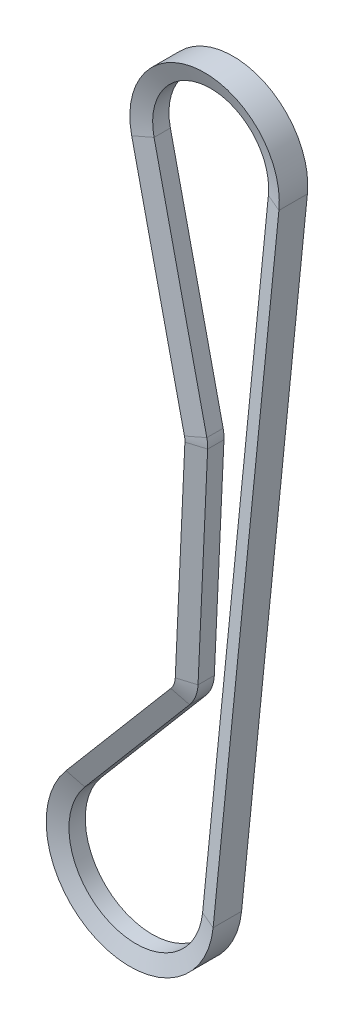
SolidWorks part; units mm, degrees
ref_plane "Front Plane" through (0, 0, 0) normal (0, 0, 1) x (1, 0, 0)
ref_plane "Top Plane" through (0, 0, 0) normal (0, 1, 0) x (1, 0, 0)
ref_plane "Right Plane" through (0, 0, 0) normal (1, 0, 0) x (0, 0, -1)
sketch "Sketch2" plane through (0, 0, 0) normal (0, 0, 1) x (1, 0, 0)
  line L0 (0, 0) -> (1, 0) construction
  line L1 (0, 0) -> (0, 1) construction
  line L12 (24.8744, -2.5024) -> (2.8551, -221.3772)
  line L14 (-46.3636, -200.4697) -> (-11.3088, -159.1135)
  line L15 (-9.8095, -155.2999) -> (-6.5871, -85.3741)
  line L16 (-6.7363, -83.6833) -> (-24.3862, -5.5056)
  arc A4 (2.8551, -221.3772) -> (-46.3636, -200.4697) centre (-25.0043, -218.5744) cw
  arc A7 (-24.3862, -5.5056) -> (24.8744, -2.5024) centre (0, 0) cw
  arc A8 (-11.3088, -159.1135) -> (-9.8095, -155.2999) centre (-16.1528, -155.0076) ccw
  arc A9 (-6.5871, -85.3741) -> (-6.7363, -83.6833) centre (-12.9304, -85.0818) ccw
ref_plane "Plane4" through (-24.3862, -5.5056, 0) normal (-0.2202, 0.9754, 0) x (0.9754, 0.2202, 0)
sketch "Sketch3" plane through (-24.3862, -5.5056, 0) normal (-0.2202, 0.9754, 0) x (0.9754, 0.2202, 0)
  line L0 (0, -4.7625) -> (0, 4.7625)
  line L1 (0, -4.7625) -> (5.588, -2.7286)
  line L2 (5.588, -2.7286) -> (5.588, 2.7286)
  line L3 (5.588, 2.7286) -> (0, 4.7625)
  line L4 (0, 0) -> (5.588, 0) construction
  dimension "D1" = 9.525
  dimension "D2" = 5.588
  dimension "D3" = 40
sweep "Sweep1" add profiles "Sketch3" path "Sketch2"
